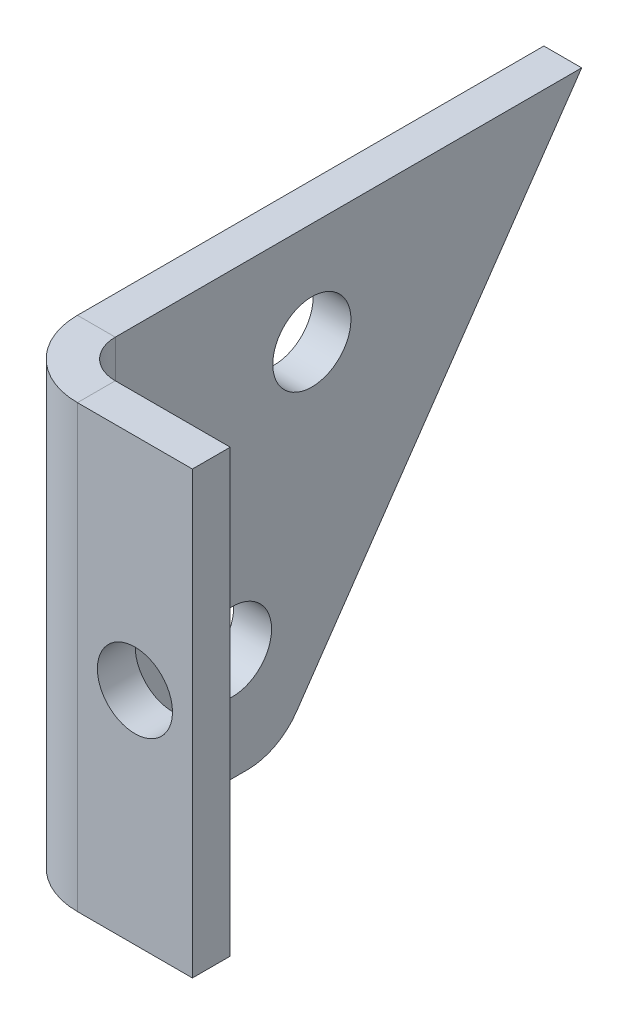
SolidWorks part; units mm, degrees
note: The reader was unsure of these and kept them because the rebuilt part matched: flange length of "Edge-Flange1".
ref_plane "Front Plane" through (0, 0, 0) normal (0, 0, 1) x (1, 0, 0)
ref_plane "Top Plane" through (0, 0, 0) normal (0, 1, 0) x (1, 0, 0)
ref_plane "Right Plane" through (0, 0, 0) normal (1, 0, 0) x (0, 0, -1)
sketch "Sketch1" plane through (0, 0, 0) normal (1, 0, 0) x (0, 0, -1)
  line L0 (71.7184, 2.1678) -> (102.9942, 47.6694)
  line L1 (0, 0) -> (95.6245, 0)
  line L5 (74.7808, 82.752) -> (14.6027, 58.2976)
  line L6 (11.5511, 53.6652) -> (11.5511, 40.2912)
  line L7 (11.5511, 40.2912) -> (48.3501, 40.2912)
  line L8 (50.1591, 38.5003) -> (50.1591, 0)
  line L9 (50.1591, 0) -> (67.5979, 0)
  line L10 (56.6677, 37) -> (96.5316, 37)
  line L11 (48.5511, 46.2861) -> (48.5511, 71.7841)
  arc A0 (67.5979, 0) -> (71.7184, 2.1678) centre (67.5979, 5) ccw
  arc A1 (102.9942, 47.6694) -> (74.7808, 82.752) centre (83.6279, 60.9809) ccw
  arc A2 (14.6027, 58.2976) -> (11.5511, 53.6652) centre (16.551, 53.6928) ccw
  arc A3 (50.1591, 38.5003) -> (48.3501, 40.2912) centre (48.3591, 38.4912) ccw
  circle A4 centre (20.4902, 52.6725) radius 3.15
  circle A5 centre (39.0112, 57.1948) radius 3.15
  circle A6 centre (66.345, 9.2223) radius 3.2825
  circle A7 centre (73.0099, 28.4056) radius 3.2825
  circle A8 centre (83.6279, 42.4814) radius 1.75
  circle A9 centre (102.3808, 60.9809) radius 1.75
  circle A10 centre (83.6279, 79.4804) radius 1.75
  circle A11 centre (83.6279, 60.9809) radius 13.8
  circle A12 centre (65.3817, 60.9809) radius 1.75
  dimension "D3" = 1.8
  dimension "D4" = 23.5
  dimension "D5" = 27.6
  dimension "D6" = 3.5
  dimension "D7" = 6.3
  dimension "D1" = 37
  dimension "D2" = 37
sketch "Sketch2" plane through (0, 0, 0) normal (1, 0, 0) x (0, 0, -1)
  line L8 (50.1591, 38.5003) -> (50.1591, 0) construction
  line L9 (0, 0) -> (95.6245, 0) construction
  line L10 (71.7184, 2.1678) -> (102.9942, 47.6694) construction
  line L11 (56.6677, 37) -> (96.5316, 37) construction
  line L12 (50.1591, 37) -> (50.1591, 0)
  line L13 (50.1591, 0) -> (67.5979, 0)
  line L14 (71.7184, 2.1678) -> (95.6605, 37)
  line L15 (50.1591, 37) -> (95.6605, 37)
  circle A6 centre (73.0099, 28.4056) radius 3.2825 construction
  circle A7 centre (66.345, 9.2223) radius 3.2825 construction
  arc A8 (67.5979, 0) -> (71.7184, 2.1678) centre (67.5979, 5) ccw construction
  circle A9 centre (73.0099, 28.4056) radius 3.2825
  circle A10 centre (66.345, 9.2223) radius 3.2825
  arc A11 (67.5979, 0) -> (71.7184, 2.1678) centre (67.5979, 5) ccw
base flange "Base-Flange1" sketch "Sketch2" thickness 3.175 reverse thickness direction no parameters "D1"=3.175
edge flange "Edge-Flange1" sketch "Sketch5" flange angle 90 flange length 12.825 flange position material inside bend radius 3.175 thickness 3.175 relief rectangular parameters "D6"=10
sketch "Sketch5" plane through (0, 0, -50.1591) normal (0, 0, 1) x (0, -1, 0)
  line L0 (-37, 0) -> (0, 0) construction
  line L1 (-37, 0) -> (0, 0)
  line L2 (-37, 0) -> (-37, 12.825)
  line L3 (-37, 12.825) -> (0, 12.825)
  line L4 (0, 12.825) -> (0, 0)
bend "EdgeBend1" bend radius 3.175 bend angle 90 parameters "D5"=1
sketch "Sketch6" plane through (0, 0, -53.3341) normal (0, 0, -1) x (-1, 0, 0)
  line L0 (-3.175, 18.5) -> (-12.825, 18.5) construction
  line L1 (-3.175, 37) -> (-3.175, 0) construction
  line L2 (-12.825, 0) -> (-12.825, 37) construction
  circle A0 centre (-8, 18.5) radius 3.15
  point P8 (0, 0)
  point P9 (-8, 18.5)
extrude "Cut-Extrude1" cut sketch "Sketch6" against normal blind 10 normal cut yes
sketch "Bend-Lines1" [suppressed] plane through (0, 0, 0) normal (0, 1, 0) x (1, 0, 0)
sketch "Bounding-Box1" [suppressed] plane through (0, 0, 0) normal (0, 1, 0) x (1, 0, 0)
sheet metal parameters "Sheet-Metal1" thickness 3.175 parameters "D1"=3.175
flat pattern "Flat-Pattern1" [suppressed]
sketch "Bend-Lines2" plane through (0, 0, 0) normal (0, 1, 0) x (1, 0, 0)
sketch3d "Bounding-Box2" [suppressed]
  line L0 (-17.4389, -5, 0) -> (28.0626, -5, 0) construction
  line L1 (-17.4389, 32, 0) -> (28.0626, 32, 0) construction
  line L2 (-17.4389, -5, 0) -> (-17.4389, 32, 0) construction
  line L3 (28.0626, -5, 0) -> (28.0626, 32, 0) construction
sheet metal parameters "Sheet-Metal4" thickness 3.175 parameters "D1"=3.175
flat pattern "Flat-Pattern1"
sketch "Bend-Lines2" plane through (0, 0, 0) normal (1, 0, 0) x (0, 0, -1)
  line L0 (54.9216, 37) -> (54.9216, 0) construction
  line L1 (54.9216, 37) -> (54.9216, 0) construction
sketch3d "Bounding-Box2" [suppressed]
  line L0 (-23.9139, -5, 0) -> (28.0626, -5, 0) construction
  line L1 (-23.9139, 32, 0) -> (28.0626, 32, 0) construction
  line L2 (-23.9139, -5, 0) -> (-23.9139, 32, 0) construction
  line L3 (28.0626, -5, 0) -> (28.0626, 32, 0) construction
bend of the flat pattern "Flatten-<EdgeBend1>1"
sheet metal parameters "Sheet-Metal5" thickness 3.175 parameters "D1"=3.175
flat pattern "Flat-Pattern1"
sketch "Bend-Lines2" plane through (0, 0, 0) normal (1, 0, 0) x (0, 0, -1)
  line L0 (54.9216, 37) -> (54.9216, 0) construction
  line L1 (54.9216, 37) -> (54.9216, 0) construction
sketch3d "Bounding-Box2" [suppressed]
  line L0 (-23.9139, -5, 0) -> (28.0626, -5, 0) construction
  line L1 (-23.9139, 32, 0) -> (28.0626, 32, 0) construction
  line L2 (-23.9139, -5, 0) -> (-23.9139, 32, 0) construction
  line L3 (28.0626, -5, 0) -> (28.0626, 32, 0) construction
bend of the flat pattern "Flatten-<EdgeBend1>1"
